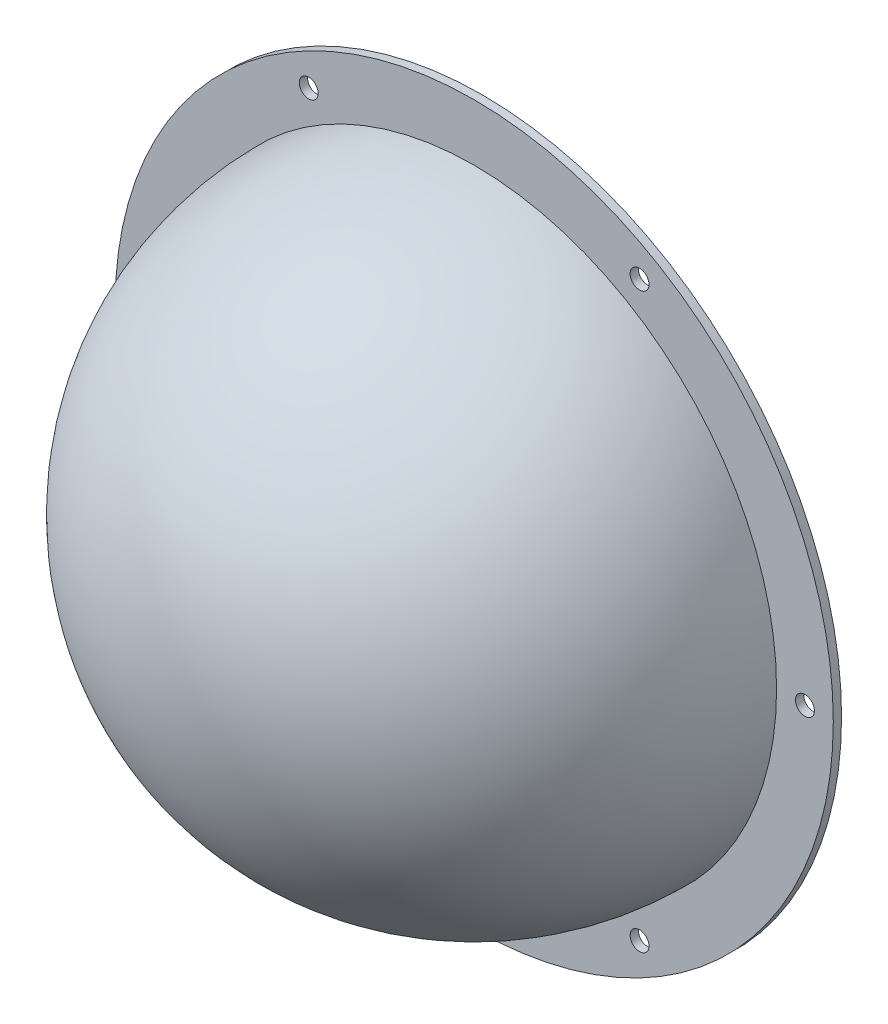
SolidWorks part; units mm, degrees
ref_plane "Front Plane" through (0, 0, 0) normal (0, 0, 1) x (1, 0, 0)
ref_plane "Top Plane" through (0, 0, 0) normal (0, 1, 0) x (1, 0, 0)
ref_plane "Right Plane" through (0, 0, 0) normal (1, 0, 0) x (0, 0, -1)
ref_axis "Z" through (0, 0, -6.727) along (0, 0, 1)
sketch "Sketch1" plane through (0, 0, 0) normal (0, 1, 0) x (1, 0, 0)
  line L0 (-101.6, 0) -> (101.6, 0) construction
  line L1 (0, 0) -> (0, -101.6) construction
  line L2 (101.6, 0) -> (101.6, -61.1188) construction
  line L3 (-61.1752, -101.6) -> (-0.8775, -101.6) construction
  line L4 (98.8219, 0) -> (98.8219, 2.7781)
  line L5 (98.8219, 2.7781) -> (120.65, 2.7781)
  line L6 (120.65, 2.7781) -> (120.65, 0)
  line L7 (120.65, 0) -> (101.6, 0)
  line L8 (0, -98.8219) -> (0, -101.6)
  arc A0 (0, -101.6) -> (101.6, 0) centre (0, 0) ccw
  arc A1 (0, -98.8219) -> (98.8219, 0) centre (0, 0) ccw
  point P14 (0, 0)
  dimension "D1" = 203.2
  dimension "D3" = 19.05
  dimension "D4" = 2.7781
revolve "Revolve1" add sketch "Sketch1" angle 360 about L1
sketch "Sketch2" plane through (0, 0, 0) normal (0, 0, 1) x (1, 0, 0)
  line L0 (101.6, 0) -> (120.65, 0) construction
  circle A0 centre (111.125, 0) radius 3.175
  point P4 (111.125, 0)
  point P7 (0, 0)
  dimension "D1" = 6.35
extrude "Cut-Extrude1" cut sketch "Sketch2" against normal through all both and the other way through all
pattern_circular "CirPattern1" count 6 over 360 about axis through (0, 0, -6.727) along (0, 0, 1) of "Cut-Extrude1"
